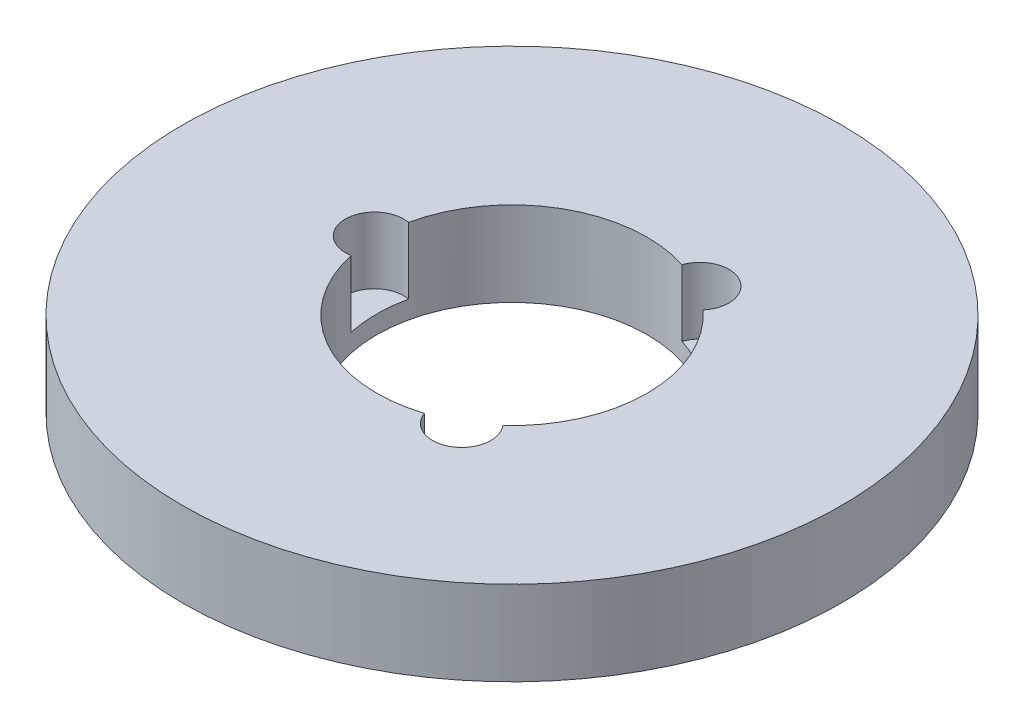
SolidWorks part; units mm, degrees
ref_plane "Front Plane" through (0, 0, 0) normal (0, 0, 1) x (1, 0, 0)
ref_plane "Top Plane" through (0, 0, 0) normal (0, 1, 0) x (1, 0, 0)
ref_plane "Right Plane" through (0, 0, 0) normal (1, 0, 0) x (0, 0, -1)
sketch "Sketch1" plane through (0, 0, 0) normal (0, 1, 0) x (1, 0, 0)
  circle A0 centre (0, 0) radius 97.5
  dimension "FLANGE_OD" = 195
extrude "Boss-Extrude1" add sketch "Sketch1" along normal blind 25
sketch "Sketch2" plane through (0, 0, 0) normal (0, 1, 0) x (1, 0, 0)
  circle A0 centre (0, 0) radius 40
  dimension "BORE_D" = 80
extrude "Cut-Extrude1" cut sketch "Sketch2" along normal through all
sketch "Sketch3" plane through (0, 25, 0) normal (0, 1, 0) x (1, 0, 0)
  circle A0 centre (0, 0) radius 40.6674 construction
  circle A1 centre (-40.6674, 0) radius 8.6364
  dimension "BOLT_D" = 17.2728
  dimension "BOLT_PCD" = 81.3347
extrude "Cut-Extrude2" cut sketch "Sketch3" against normal blind 19.6569
pattern_circular "CirPattern1" count 3 over 360 about axis through (0, 0, 0) along (0, 1, 0) of "Cut-Extrude2"
